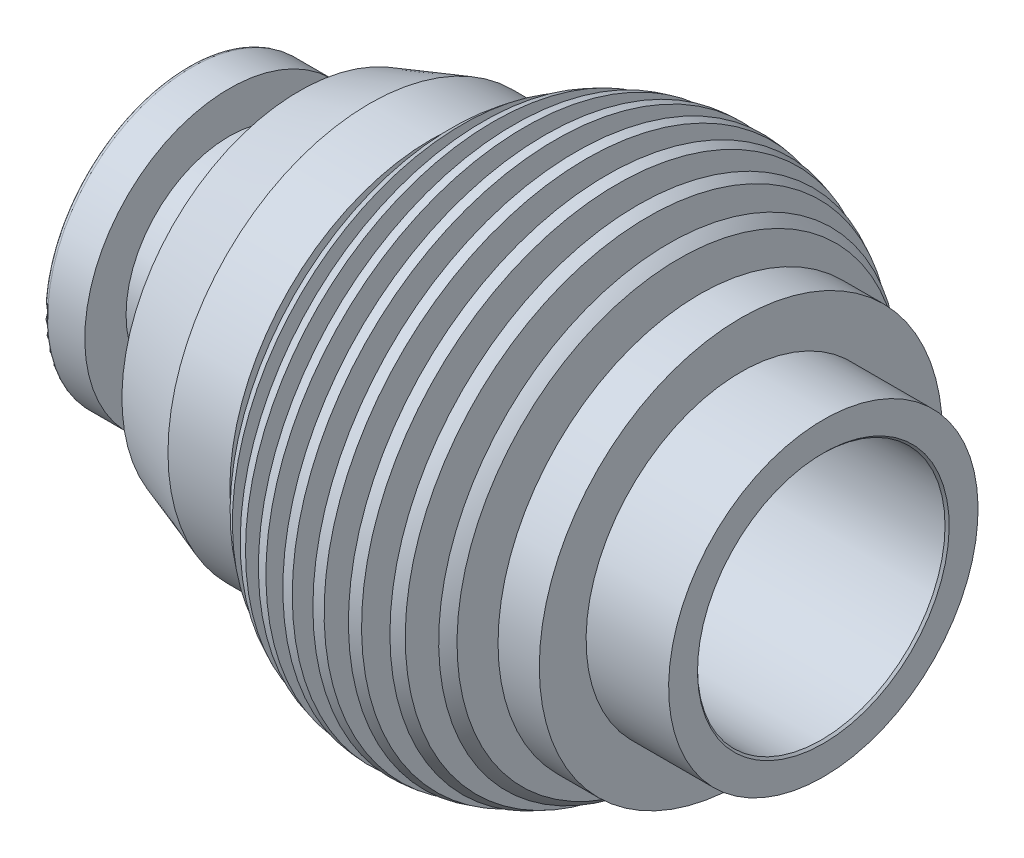
SolidWorks part; units mm, degrees
ref_plane "Front Plane" through (0, 0, 0) normal (0, 0, 1) x (1, 0, 0)
ref_plane "Top Plane" through (0, 0, 0) normal (0, 1, 0) x (1, 0, 0)
ref_plane "Right Plane" through (0, 0, 0) normal (1, 0, 0) x (0, 0, -1)
sketch "Sketch1" plane through (0, 0, 0) normal (0, 0, 1) x (1, 0, 0)
  line L0 (-113.7651, 0) -> (67.2575, 0) construction
  line L1 (0, 15) -> (54, 15)
  line L2 (0, 15) -> (0, 35)
  line L3 (0, 35) -> (10, 35)
  line L4 (10, 35) -> (10, 25)
  line L5 (10, 25) -> (17, 25)
  line L6 (27, 35) -> (27, 43)
  line L7 (27, 43) -> (44.0193, 48.8602)
  line L8 (44.0193, 48.8602) -> (59.0193, 48.8602)
  line L9 (54, 15) -> (54, 30)
  line L10 (54, 30) -> (154, 30)
  line L11 (154, 30) -> (154, 37.5)
  line L12 (154, 37.5) -> (134, 37.5)
  line L13 (134, 37.5) -> (134.0193, 48.86)
  line L14 (134.0193, 48.86) -> (124.0193, 48.86)
  line L17 (59.0193, 48.8602) -> (59.0193, 40)
  line L18 (59.0193, 40) -> (64.0193, 40)
  line L19 (64.0193, 53.807) -> (64.0193, 40)
  line L21 (66.5193, 55.7504) -> (66.5193, 40)
  line L22 (66.5193, 40) -> (71.5193, 40)
  line L23 (71.5193, 58.8504) -> (71.5193, 40)
  line L25 (74.0193, 60.0695) -> (74.0193, 40)
  line L26 (74.0193, 40) -> (79.0193, 40)
  line L27 (79.0193, 61.9447) -> (79.0193, 40)
  line L29 (81.5193, 62.6261) -> (81.5193, 40)
  line L30 (81.5193, 40) -> (86.5193, 40)
  line L31 (86.5193, 63.5176) -> (86.5193, 40)
  line L33 (89.0193, 63.7376) -> (89.0193, 40)
  line L34 (89.0193, 40) -> (94.0193, 40)
  line L35 (94.0193, 63.7376) -> (94.0193, 40)
  line L37 (96.5193, 63.5176) -> (96.5193, 40)
  line L38 (96.5193, 40) -> (101.5193, 40)
  line L39 (101.5193, 62.6261) -> (101.5193, 40)
  line L41 (104.0193, 61.9446) -> (104.0193, 40)
  line L42 (104.0193, 40) -> (109.0193, 40)
  line L43 (109.0193, 60.0695) -> (109.0193, 40)
  line L45 (111.5193, 58.8503) -> (111.5193, 40)
  line L46 (111.5193, 40) -> (116.5193, 40)
  line L47 (116.5193, 55.7502) -> (116.5193, 40)
  line L49 (119.0193, 53.8068) -> (119.0193, 40)
  line L50 (119.0193, 40) -> (124.0193, 40)
  line L51 (124.0193, 48.86) -> (124.0193, 40)
  arc A0 (17, 25) -> (27, 35) centre (17, 35) ccw
  arc A3 (119.0193, 53.8068) -> (116.5193, 55.7502) centre (91.5192, 21.0107) ccw
  arc A4 (66.5193, 55.7504) -> (64.0193, 53.807) centre (91.5192, 21.0107) ccw
  arc A5 (74.0193, 60.0695) -> (71.5193, 58.8504) centre (91.5192, 21.0107) ccw
  arc A6 (81.5193, 62.6261) -> (79.0193, 61.9447) centre (91.5192, 21.0107) ccw
  arc A7 (89.0193, 63.7376) -> (86.5193, 63.5176) centre (91.5192, 21.0107) ccw
  arc A8 (96.5193, 63.5176) -> (94.0193, 63.7376) centre (91.5192, 21.0107) ccw
  arc A9 (104.0193, 61.9446) -> (101.5193, 62.6261) centre (91.5192, 21.0107) ccw
  arc A10 (111.5193, 58.8503) -> (109.0193, 60.0695) centre (91.5192, 21.0107) ccw
  arc A12 (124.0193, 48.86) -> (59.0193, 48.8602) centre (91.5192, 21.0107) ccw
  dimension "D6" = 10
  dimension "D16" = 15
  dimension "D18" = 42.8
  dimension "D1" = 100
  dimension "D2" = 54
  dimension "D3" = 20
  dimension "D4" = 10
  dimension "D5" = 10
  dimension "D7" = 8
  dimension "D8" = 18
  dimension "D9" = 15
  dimension "D10" = 161
  dimension "D11" = 10
  dimension "D12" = 20
  dimension "D13" = 7.5
  dimension "D14" = 18.86
  dimension "D15" = 15
  dimension "D17" = 17
  dimension "D19" = 10
  dimension "D20" = 5
  dimension "D21" = 2.5
  dimension "D22" = 2.5
  dimension "D23" = 2.5
  dimension "D24" = 2.5
  dimension "D25" = 2.5
  dimension "D26" = 2.5
  dimension "D27" = 2.5
  dimension "D28" = 2.5
revolve "Revolve1" add sketch "Sketch1" angle 360 about L0 region at (68.4388, 34.669, 0)
sketch "Sketch4" plane through (0, 0, 0) normal (0, 1, 0) x (1, 0, 0)
  line L0 (91.5193, 40) -> (91.5193, -40) construction
  line L1 (89.0193, 40) -> (94.0193, 40) construction
  line L2 (89.0193, 40) -> (89.0193, -40) construction
  line L3 (89.0193, -40) -> (94.0193, -40) construction
  line L4 (94.0193, 40) -> (94.0193, -40) construction
  line L5 (89.0193, -40) -> (94.0193, -40) construction
  circle A0 centre (91.5193, 0) radius 7.5
  dimension "D1" = 15
extrude "Cut-Extrude1" cut sketch "Sketch4" against normal through all
sketch "Sketch7" plane through (27, 0, 0) normal (-1, 0, 0) x (0, 0, 1)
  circle A1 centre (0, 39) radius 2.5
  circle A2 centre (0, 0) radius 39
  circle A3 centre (0, 0) radius 39 construction
  dimension "D1" = 4
hole_wizard "Ø5.0 mm Dowel Holes3" positions "Sketch10" profile "Sketch11" hole size "Ø5.0" standard "ISO"
sketch "Sketch10" plane through (27, 0, 0) normal (-1, 0, 0) x (0, 0, 1)
  circle A4 centre (0, 0) radius 39
  circle A5 centre (0, 0) radius 39
  point P16 (0, 39)
  dimension "D1" = 4
sketch "Sketch11" plane through (27, 39, 0) normal (0, 1, 0) x (0, 0, 1)
  line L0 (0, 0) -> (0, 21.5022)
  line L1 (0, 21.5022) -> (2.5, 20)
  line L2 (2.5, 20) -> (2.5, 0.2098)
  line L3 (2.5, 0.2098) -> (2.75, 0)
  line L5 (2.75, 0) -> (0, 0)
  line L6 (-2.5, 0.2098) -> (-2.75, 0) construction
  line L10 (0, 21.5022) -> (-2.5, 20) construction
  line L11 (0, -6.35) -> (0, 107.95) construction
  dimension "Hole Dia." = 5
  dimension "Hole Depth" = 20
  dimension "Near C'Sink Dia." = 5.5
  dimension "Near C'Sink Angle" = 100
  dimension "Drill Angle" = 118
ref_axis "Axis1" through (54, 0, 0) along (-1, 0, 0)
pattern_circular "CirPattern1" count 9 over 360 about axis through (54, 0, 0) along (-1, 0, 0) of "Ø5.0 mm Dowel Holes3"
chamfer "Chamfer1" distance 0.5 angle 45 2 edges at (0, -15, 0) (154, -30, 0)
fillet "Fillet2" radius 1 2 edges at (0, -35, 0) (0, -15.5, 0)
